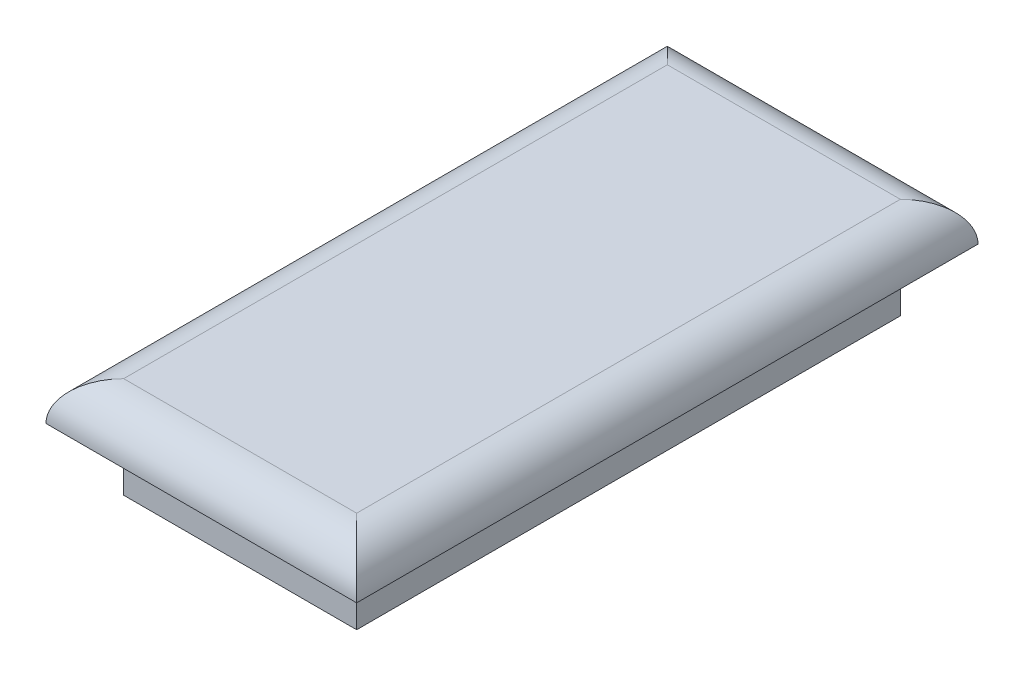
SolidWorks part; units mm, degrees
ref_plane "Front Plane" through (0, 0, 0) normal (0, 0, 1) x (1, 0, 0)
ref_plane "Top Plane" through (0, 0, 0) normal (0, 1, 0) x (1, 0, 0)
ref_plane "Right Plane" through (0, 0, 0) normal (1, 0, 0) x (0, 0, -1)
sketch "Sketch1" plane through (0, 0, 0) normal (0, 1, 0) x (1, 0, 0)
  line L1 (-9.525, -22.225) -> (9.525, -22.225)
  line L2 (-9.525, -22.225) -> (-9.525, 22.225)
  line L3 (-9.525, 22.225) -> (9.525, 22.225)
  line L4 (9.525, -22.225) -> (9.525, 22.225)
  line L5 (-9.525, -22.225) -> (9.525, 22.225) construction
  line L6 (-9.525, 22.225) -> (9.525, -22.225) construction
  point P0 (0, 0)
  dimension "D1" = 19.05
  dimension "D2" = 44.45
extrude "Boss-Extrude1" add sketch "Sketch1" along normal blind 5.08
sketch "Sketch2" plane through (0, 5.08, 0) normal (0, 1, 0) x (1, 0, 0)
  line L0 (-9.525, 22.225) -> (-9.525, -22.225) construction
  line L1 (-12.7, -25.4) -> (12.7, -25.4)
  line L2 (-12.7, -25.4) -> (-12.7, 25.4)
  line L3 (-12.7, 25.4) -> (12.7, 25.4)
  line L4 (12.7, -25.4) -> (12.7, 25.4)
  line L5 (-12.7, -25.4) -> (12.7, 25.4) construction
  line L6 (-12.7, 25.4) -> (12.7, -25.4) construction
  line L7 (9.525, 22.225) -> (-9.525, 22.225) construction
  point P0 (0, 0)
  dimension "D1" = 3.175
  dimension "D2" = 3.175
extrude "Boss-Extrude2" add sketch "Sketch2" along normal blind 3.175
fillet "Fillet1" radius 3.175 4 edges at (0, 8.255, -25.4) (-12.7, 8.255, 0) (0, 8.255, 25.4) (12.7, 8.255, 0)
sketch "Sketch3" plane through (9.525, 0, 0) normal (1, 0, 0) x (0, 0, -1)
  line L0 (-22.225, 2.54) -> (22.225, 2.54) construction
  line L1 (-22.225, 5.08) -> (-22.225, 0) construction
  line L2 (22.225, 5.08) -> (22.225, 0) construction
  point P6 (0, 2.54)
hole_wizard "Tap Drill for M3x0.5 Tap1" [suppressed] positions "3DSketch1" profile "Sketch4" hole size "M3x0.5" standard "ANSI Metric"
sketch3d "3DSketch1"
  point P0 (9.525, 2.54, 0)
sketch "Sketch4" plane through (9.525, 2.54, 0) normal (0, 1, 0) x (0, 0, -1)
  line L0 (0, 0) -> (0, 22.225)
  line L1 (0, 22.225) -> (1.25, 22.225)
  line L2 (1.25, 22.225) -> (1.25, 0)
  line L5 (1.25, 0) -> (0, 0)
  line L11 (0, -6.35) -> (0, 107.95) construction
  dimension "Thru Hole Dia." = 2.5
  dimension "Thru Hole Depth" = 22.225
equation "\"D2@Sketch2\"=\"D1@Sketch2\""
